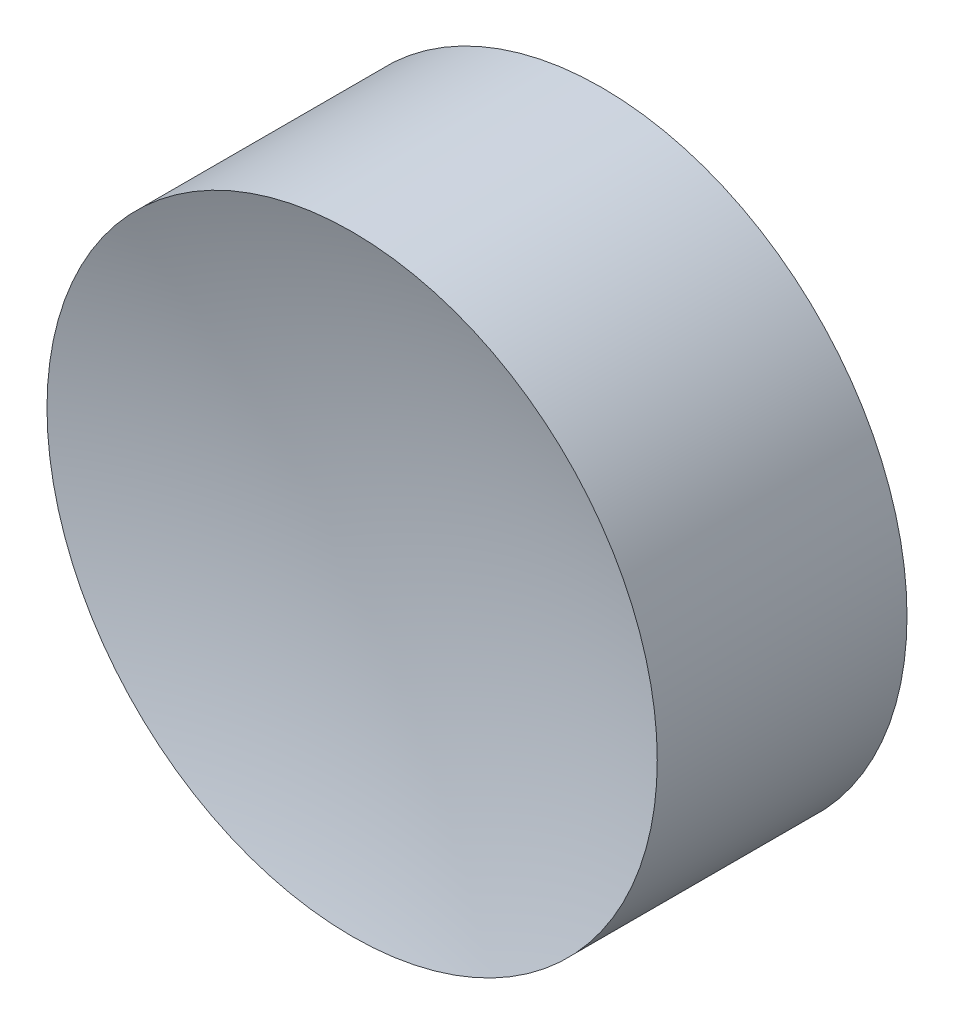
SolidWorks part; units mm, degrees
ref_plane "Ebene vorne" through (0, 0, 0) normal (0, 0, 1) x (1, 0, 0)
ref_plane "Ebene oben" through (0, 0, 0) normal (0, 1, 0) x (1, 0, 0)
ref_plane "Ebene rechts" through (0, 0, 0) normal (1, 0, 0) x (0, 0, -1)
other "Massenmittelpunkt"
sketch "Skizze1" plane through (0, 0, 0) normal (0, 1, 0) x (1, 0, 0)
  line L0 (0, 0.75) -> (0, -0.75)
  line L1 (3, -1.2276) -> (3, 1.2276)
  line L2 (0, 1.2276) -> (0, -1.2276) construction
  arc A0 (3, 1.2276) -> (0, 0.75) centre (0, 10.41) cw
  arc A1 (0, -0.75) -> (3, -1.2276) centre (0, -10.41) cw
revolve "Rotation1" add sketch "Skizze1" angle 360 about L2 reverse direction yes
ref_plane "Ebene1" through (3, 0, 0) normal (1, 0, 0) x (0, 0, -1)
ref_axis "Achse2" through (-3.3, 0, 0) along (1, 0, 0)
ref_point "Punkt1"
ref_axis "ASS_Opitcal_Axis" through (0, 0, -1.2276) along (0, 0, 1)
ref_plane "Ebene2" through (-3, 0, 0) normal (-1, 0, 0) x (0, 0, 1)
ref_point "Punkt2"
ref_point "Punkt3"
